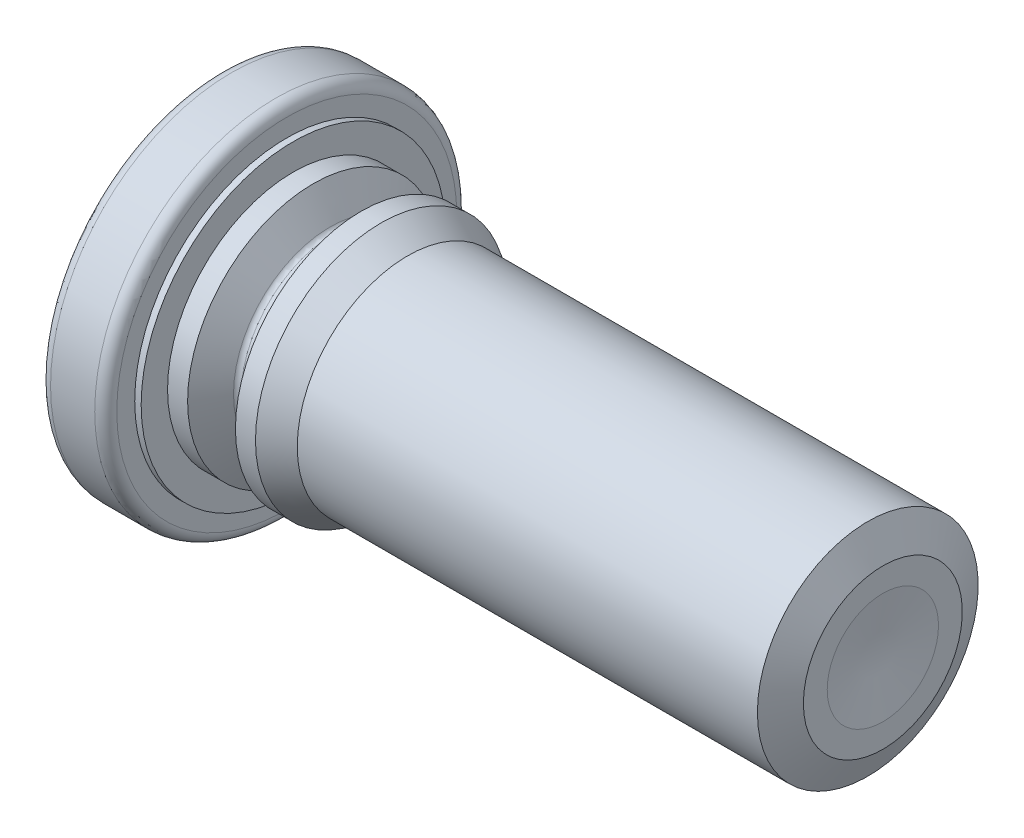
SolidWorks part; units mm, degrees
ref_plane "Front" through (0, 0, 0) normal (0, 0, 1) x (1, 0, 0)
ref_plane "Top" through (0, 0, 0) normal (0, 1, 0) x (1, 0, 0)
ref_plane "Right" through (0, 0, 0) normal (1, 0, 0) x (0, 0, -1)
sketch "Sketch1" plane through (0, 0, 0) normal (0, 0, 1) x (1, 0, 0)
  line L0 (-4.7625, 0) -> (4.7625, 0) construction
  line L1 (-4.7625, 0) -> (-4.7625, 2.6035)
  line L2 (-4.7625, 2.6035) -> (-3.81, 2.6035)
  line L3 (-3.81, 2.6035) -> (-3.81, 2.1869)
  line L4 (-3.81, 2.1869) -> (-3.7174, 2.1869)
  line L5 (-3.7174, 2.1869) -> (-3.7174, 1.8075)
  line L6 (-3.1645, 1.3494) -> (-3.0058, 1.3494)
  line L7 (-3.429, 1.8075) -> (-3.429, 1.3494) construction
  line L8 (-2.0719, 1.5875) -> (4.5457, 1.5875)
  line L9 (4.5457, 1.5875) -> (4.7625, 1.143)
  line L10 (4.7625, 1.143) -> (4.7625, 0.8001)
  line L11 (-4.7625, 0) -> (4.6541, 0)
  line L12 (4.7625, 0.8001) -> (4.6541, 0)
  line L13 (4.6541, 1.3653) -> (4.6541, 0) construction
  line L14 (-2.0719, 1.5875) -> (-2.4529, 1.8075)
  line L15 (-2.4529, 1.3494) -> (-3.0058, 1.3494) construction
  line L16 (-3.7174, 1.8075) -> (-3.429, 1.8075)
  line L17 (-3.429, 1.3494) -> (-3.1645, 1.3494) construction
  line L18 (-2.4529, 1.8075) -> (-2.4529, 1.3494) construction
  line L19 (-3.429, 1.8075) -> (-3.1645, 1.3494)
  line L21 (-2.4529, 1.8075) -> (-2.7413, 1.8075)
  line L22 (-2.7413, 1.8075) -> (-3.0058, 1.3494)
  dimension "D2" = 64
  dimension "D" = 2.286
  dimension "D1" = 2.6987
  dimension "D3" = 0.9525
  dimension "D5" = 1.6002
  dimension "D6" = 0.381
  dimension "D7" = 0.381
  dimension "D8" = 0.0926
  dimension "D9" = 30
  dimension "D10" = 2.1869
  dimension "D11" = 30
  dimension "D4" = 0.1587
revolve "Revolve1" add sketch "Sketch1" angle 360 about L0
fillet "Fillet1" radius 0.1587 2 edges at (-3.81, 0, 2.6035) (-4.7625, 0, 2.6035)
fillet "Fillet2" radius 0.0794 2 edges at (-3.1645, 0, 1.3494) (-3.0058, 0, 1.3494)
ref_axis "Center Axis 1" through (4.5457, 0, 0) along (-1, 0, 0)
ref_plane "Contact Plane 1" through (4.7625, 0, 0) normal (1, 0, 0) x (0, 0, -1)
ref_plane "Contact Plane 2" through (-4.7625, 0, 0) normal (-1, 0, 0) x (0, 0, 1)
equation "\"D1@Sketch1\" = \"P@Sketch1\"*.85"
equation "\"D3@Sketch1\" = \"L@Sketch1\"/10"
equation "\"D5@Sketch1\" = \"D@Sketch1\"*.7"
equation "\"D1@Fillet1\" = \"D3@Sketch1\"/6"
equation "\"D1@Fillet2\"=(\"P@Sketch1\"-\"D1@Sketch1\")/6"
equation "\"D10@Sketch1\"=\"H@Sketch1\"*.42"
equation "\"D4@Sketch1\"=\"D3@Sketch1\"/6"
